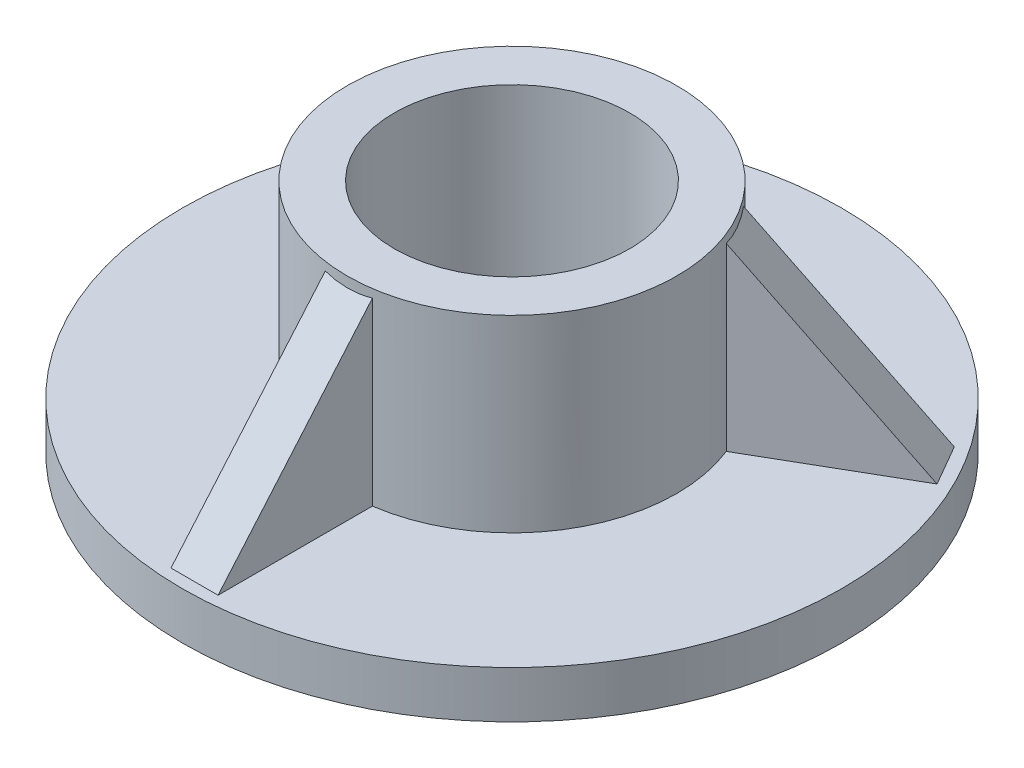
SolidWorks part; units mm, degrees
ref_plane "前视基准面" through (0, 0, 0) normal (0, 0, 1) x (1, 0, 0)
ref_plane "上视基准面" through (0, 0, 0) normal (0, 1, 0) x (1, 0, 0)
ref_plane "右视基准面" through (0, 0, 0) normal (1, 0, 0) x (0, 0, -1)
sketch "草图1" plane through (0, 0, 0) normal (0, 1, 0) x (1, 0, 0)
  circle A0 centre (0, 0) radius 70
  circle A1 centre (0, 0) radius 25
  circle A2 centre (0, 0) radius 35
  dimension "D1" = 140
  dimension "D2" = 50
  dimension "D3" = 70
extrude "凸台-拉伸1" add sketch "草图1" along normal blind 10 contours A0 A2 region at (-68.0201, 0, 0)
extrude "凸台-拉伸2" add sketch "草图1<3>" along normal blind 50 contours A2 A1 region at (-34.0101, 0, 0)
sketch "草图1<3>" plane through (0, 0, 0) normal (0, 1, 0) x (1, 0, 0) same geometry as "草图1"
sketch "草图2" plane through (0, 0, 0) normal (1, 0, 0) x (0, 0, -1)
  line L0 (-35, 47.8197) -> (-67.4053, 10)
  line L6 (-35, 50) -> (-35, 10) construction
  line L7 (70, 10) -> (-70, 10) construction
rib "筋13" sketch "草图2" sketch "草图2" thickness 10 extrusion direction parallel to sketch draft on no parameters "D1"=10
pattern_circular "阵列(圆周)1" count 3 over 360 about axis through (0, 50, 0) along (0, -1, 0) of "筋13"
